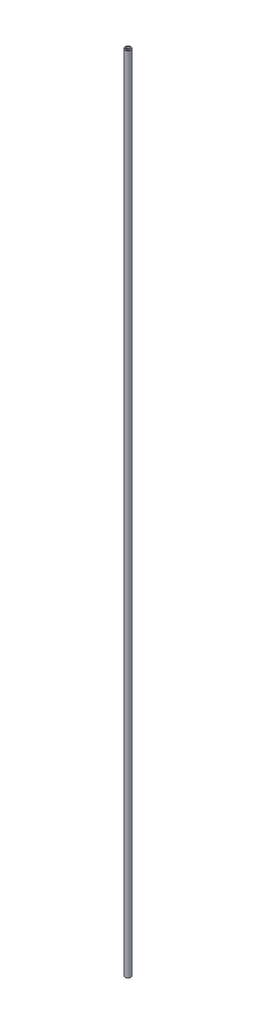
SolidWorks part; units mm, degrees
material "acero"
ref_plane "Alzado" through (0, 0, 0) normal (0, 0, 1) x (1, 0, 0)
ref_plane "Planta" through (0, 0, 0) normal (0, 1, 0) x (1, 0, 0)
ref_plane "Vista lateral" through (0, 0, 0) normal (1, 0, 0) x (0, 0, -1)
sketch "Croquis6" plane through (0, 0, 0) normal (0, 0, 1) x (1, 0, 0)
  line L0 (0, 0) -> (0, 100)
  line L4 (370.98, 211.34) -> (370.98, 86)
  arc A0 (0, 100) -> (14.4473, 246.5) centre (750, 100) cw
  arc A1 (14.4473, 246.5) -> (370.98, 211.34) centre (190.98, 211.34) cw
  dimension "D1" = 180
  dimension "D2" = 750
  dimension "D3" = 146.5
  dimension "D4" = 100
  dimension "D5" = 86
sketch "Croquis7" plane through (0, 0, 0) normal (0, 1, 0) x (1, 0, 0)
  circle A0 centre (0, 0) radius 3.175
  circle A1 centre (0, 0) radius 1.585
  dimension "D1" = 6.35
  dimension "D2" = 3.17
sweep "Barrer4" add profiles "Croquis7" path "Croquis6"
chamfer "Chaflán2" distance 1 angle 30 2 edges at (0, 0, 1.585) (370.98, 86, 1.585) first distance on face at (0, 100, 1.585) first distance on face at (370.98, 211.34, 1.585)
extrude "Saliente-Extruir2" add sketch "Croquis7<3>" along normal blind 855 separate body
sketch "Croquis7<3>" plane through (0, 0, 0) normal (0, 1, 0) x (1, 0, 0) same geometry as "Croquis7"
delete or keep bodies "Sólido-Eliminar1" type delete bodies bodies 109
delete or keep bodies "Sólido-Eliminar2" [suppressed] type delete bodies bodies 110
chamfer "Chaflán3" distance 1 angle 30 2 edges at (0, 0, 1.585) (0, 855, 1.585) first distance on face at (0, 855, 1.585)
